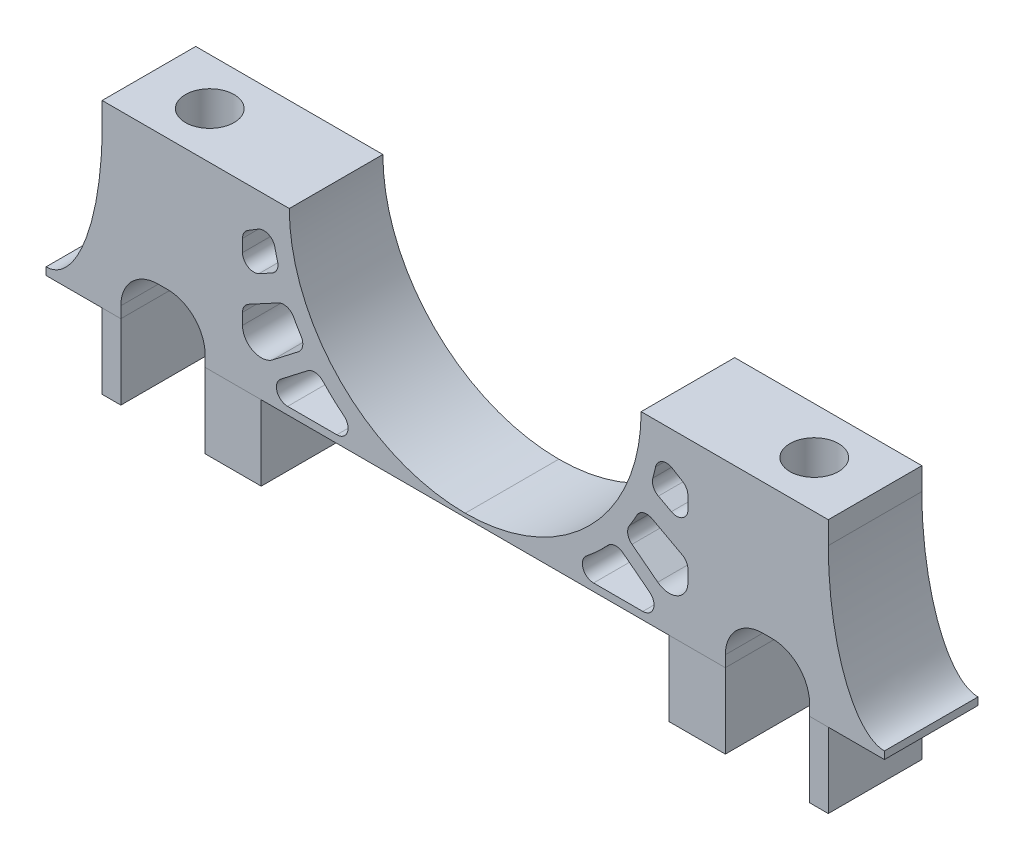
SolidWorks part; units mm, degrees
material "1060 Alloy"
ref_plane "Front Plane" through (0, 0, 0) normal (0, 0, 1) x (1, 0, 0)
ref_plane "Top Plane" through (0, 0, 0) normal (0, 1, 0) x (1, 0, 0)
ref_plane "Right Plane" through (0, 0, 0) normal (1, 0, 0) x (0, 0, -1)
sketch "Sketch1" plane through (0, 0, 0) normal (0, 0, 1) x (1, 0, 0)
  line L5 (-49.276, 0.508) -> (-49.276, 12.192)
  line L6 (0, 0.508) -> (0, 12.192)
  line L7 (-49.276, 12.192) -> (-36.576, 12.192)
  line L8 (0, 12.192) -> (-12.7, 12.192)
  line L9 (0, 0) -> (0, -5.08)
  line L10 (0, -5.08) -> (-1.27, -5.08)
  line L11 (-10.795, -5.08) -> (-10.795, 0)
  line L12 (-10.795, 0) -> (-38.481, 0)
  line L13 (-38.481, 0) -> (-38.481, -5.08)
  line L15 (-49.276, -5.08) -> (-49.276, 0)
  line L16 (-24.638, 0.254) -> (-24.638, 0) construction
  line L17 (-1.27, -5.08) -> (-1.27, 3.302)
  line L18 (-1.27, 3.302) -> (-6.985, 3.302)
  line L19 (-6.985, 3.302) -> (-6.985, -5.08)
  line L20 (-48.006, -5.08) -> (-48.006, 3.302)
  line L21 (-48.006, 3.302) -> (-42.291, 3.302)
  line L22 (-42.291, 3.302) -> (-42.291, -5.08)
  line L23 (-6.985, -5.08) -> (-10.795, -5.08)
  line L24 (-38.481, -5.08) -> (-42.291, -5.08)
  line L25 (-48.006, -5.08) -> (-49.276, -5.08)
  line L26 (-18.4788, 0.508) -> (-10.3556, 0.508)
  line L27 (-10.7589, 10.922) -> (-9.525, 10.922) construction
  line L28 (-9.525, 10.922) -> (-9.525, 10.1704) construction
  line L32 (-14.1886, 4.1135) -> (-9.525, 0.508) construction
  line L33 (-10.3556, 0.508) -> (-14.5071, 3.7176)
  line L34 (-9.525, 1.1501) -> (-13.8857, 4.5214)
  line L35 (-11.5461, 2.7126) -> (-12.1675, 1.9089) construction
  line L36 (-10.3556, 0.508) -> (-9.525, 0.508) construction
  line L37 (-9.525, 1.1501) -> (-9.525, 0.508) construction
  line L43 (-12.3425, 7.368) -> (-9.525, 5.8491) construction
  line L44 (-9.525, 4.9601) -> (-12.6511, 6.6454)
  line L45 (-9.525, 6.7381) -> (-12.0774, 8.1077)
  line L47 (-9.525, 6.7381) -> (-9.525, 4.9601) construction
  line L48 (-9.525, 4.9601) -> (-9.525, 1.1501)
  line L57 (-11.4912, 10.922) -> (-9.525, 9.7242) construction
  line L60 (-11.5382, 10.5045) -> (-9.525, 9.2781)
  line L61 (-11.4912, 10.922) -> (-10.7589, 10.922) construction
  line L62 (-10.7589, 10.922) -> (-9.525, 10.1704) construction
  line L63 (-10.7063, 9.9977) -> (-10.3099, 10.6485) construction
  line L64 (-9.525, 10.1704) -> (-9.525, 9.2781) construction
  line L65 (-9.525, 9.2781) -> (-9.525, 6.7381)
  line L69 (-39.751, 9.2781) -> (-39.751, 6.7381)
  line L70 (-37.7378, 10.5045) -> (-39.751, 9.2781)
  line L71 (-39.751, 6.7381) -> (-37.1986, 8.1077)
  line L72 (-39.751, 4.9601) -> (-39.751, 1.1501)
  line L73 (-39.751, 4.9601) -> (-36.6249, 6.6454)
  line L74 (-39.751, 1.1501) -> (-35.3903, 4.5214)
  line L75 (-30.7972, 0.508) -> (-38.9204, 0.508)
  line L76 (-38.9204, 0.508) -> (-34.7689, 3.7176)
  line L77 (0, 0) -> (3.81, 0)
  line L78 (3.81, 0) -> (3.81, 0.508)
  line L79 (3.81, 0.508) -> (0, 0.508)
  line L80 (-49.276, 0) -> (-53.086, 0)
  line L81 (-53.086, 0) -> (-53.086, 0.508)
  line L82 (-53.086, 0.508) -> (-49.276, 0.508)
  arc A0 (-36.576, 12.192) -> (-12.7, 12.192) centre (-24.638, 12.192) ccw
  arc A1 (-18.4788, 0.508) -> (-14.5071, 3.7176) centre (-24.638, 12.192) ccw
  arc A3 (-14.5071, 3.7176) -> (-13.8857, 4.5214) centre (-24.638, 12.192) ccw construction
  arc A4 (-13.8857, 4.5214) -> (-12.6511, 6.6454) centre (-24.638, 12.192) ccw
  arc A7 (-12.6511, 6.6454) -> (-12.0774, 8.1077) centre (-24.638, 12.192) ccw construction
  arc A8 (-12.0774, 8.1077) -> (-11.5382, 10.5045) centre (-24.638, 12.192) ccw
  arc A12 (-11.5382, 10.5045) -> (-11.4912, 10.922) centre (-24.638, 12.192) ccw construction
  arc A13 (-37.1986, 8.1077) -> (-37.7378, 10.5045) centre (-24.638, 12.192) cw
  arc A14 (-35.3903, 4.5214) -> (-36.6249, 6.6454) centre (-24.638, 12.192) cw
  arc A15 (-30.7972, 0.508) -> (-34.7689, 3.7176) centre (-24.638, 12.192) cw
  point P40 (-11.8568, 2.3108)
  point P64 (-10.5081, 10.3231)
  dimension "D4" = 23.876
  dimension "D1" = 12.7
  dimension "D2" = 0.254
  dimension "D6" = 5.715
  dimension "D8" = 1.27
  dimension "D3" = 5.08
  dimension "D5" = 1.27
  dimension "D7" = 8.89
  dimension "D9" = 1.27
  dimension "D10" = 0.508
  dimension "D11" = 1.016
  dimension "D12" = 1.778
  dimension "D13" = 0.762
  dimension "D14" = 0.508
  dimension "D15" = 3.81
  dimension "D16" = 3.81
  dimension "D17" = 2.54
  dimension "D18" = 3.81
  dimension "D19" = 2.54
extrude "Boss-Extrude1" add sketch "Sketch1" along normal blind 6.35
fillet "Fillet2" radius 2.54 4 edges at (-48.006, 3.302, 3.175) (-42.291, 3.302, 3.175) (-1.27, 3.302, 3.175) (-6.985, 3.302, 3.175)
fillet "Fillet5" radius 3.81 2 edges at (0, 0.508, 3.175) (-49.276, 0.508, 3.175)
fillet "Fillet3" radius 0.762 20 edges at (-10.3556, 0.508, 3.175) (-14.5071, 3.7176, 3.175) (-18.4788, 0.508, 3.175) (-13.8857, 4.5214, 3.175) (-12.0774, 8.1077, 3.175) (-12.6511, 6.6454, 3.175) (-9.525, 4.9601, 3.175) (-9.525, 9.2781, 3.175) (-11.5382, 10.5045, 3.175) (-30.7972, 0.508, 3.175) (-38.9204, 0.508, 3.175) (-39.751, 4.9601, 3.175) (-39.751, 6.7381, 3.175) (-37.7378, 10.5045, 3.175) (-39.751, 9.2781, 3.175) (-37.1986, 8.1077, 3.175) (-34.7689, 3.7176, 3.175) (-35.3903, 4.5214, 3.175) (-36.6249, 6.6454, 3.175) (-9.525, 6.7381, 3.175)
fillet "Fillet4" radius 1.27 2 edges at (-39.751, 1.1501, 3.175) (-9.525, 1.1501, 3.175)
ref_plane "Plane1" through (-24.638, 0.254, 0) normal (-1, 0, 0) x (0, 0, 1)
sketch "Sketch2" plane through (0, 12.192, 0) normal (0, 1, 0) x (1, 0, 0)
  line L5 (-1.27, -6.35) -> (-1.27, 0) construction
  line L8 (-6.985, -6.35) -> (-6.985, 0) construction
  line L9 (-1.27, -6.35) -> (-1.27, 0) construction
  line L10 (-6.985, -6.35) -> (-6.985, 0) construction
  line L11 (-6.985, -3.175) -> (-1.27, -3.175) construction
  circle A0 centre (-4.1275, -3.175) radius 2.0828
  dimension "D1" = 4.1656
hole_wizard "M4x0.7 Tapped Hole1" positions "Sketch6" profile "Sketch7" tap size "M4x0.7" standard "ANSI Metric" end condition through all
sketch "Sketch6" plane through (0, 12.192, 0) normal (0, 1, 0) x (1, 0, 0)
  point P0 (-4.1275, -3.175)
  point P4 (-4.1275, -3.175)
cosmetic thread "Hole Thread1" parameters "D2"=4
sketch "Sketch7" plane through (-4.1275, 12.192, 3.175) normal (1, 0, 0) x (0, 0, 1)
  line L0 (0, 0) -> (0, 17.272)
  line L1 (0, 17.272) -> (1.65, 17.272)
  line L2 (1.65, 17.272) -> (1.65, 0)
  line L5 (1.65, 0) -> (0, 0)
  line L11 (0, -6.35) -> (0, 107.95) construction
  dimension "Thru Tap Drill Dia." = 3.3
  dimension "Thru Tap Drill Depth" = 17.272
ref_plane "Plane3" through (-24.638, 0, 0) normal (1, 0, 0) x (0, 0, -1)
mirror "Mirror1" about plane through (-24.638, 0, 0) normal (1, 0, 0) of "M4x0.7 Tapped Hole1"
cosmetic thread "Hole Thread2" parameters "D2"=4
sketch "Sketch5" plane through (-24.638, 0.254, 0) normal (-1, 0, 0) x (0, 0, 1)
  line L0 (0, 0) -> (6.35, 0)
  line L1 (0, 0) -> (6.35, 0)
split line "Split Line2"
ref_plane "Plane2" through (0, 0, 0) normal (0, -1, 0) x (-1, 0, 0)
split line "Split Line4"
